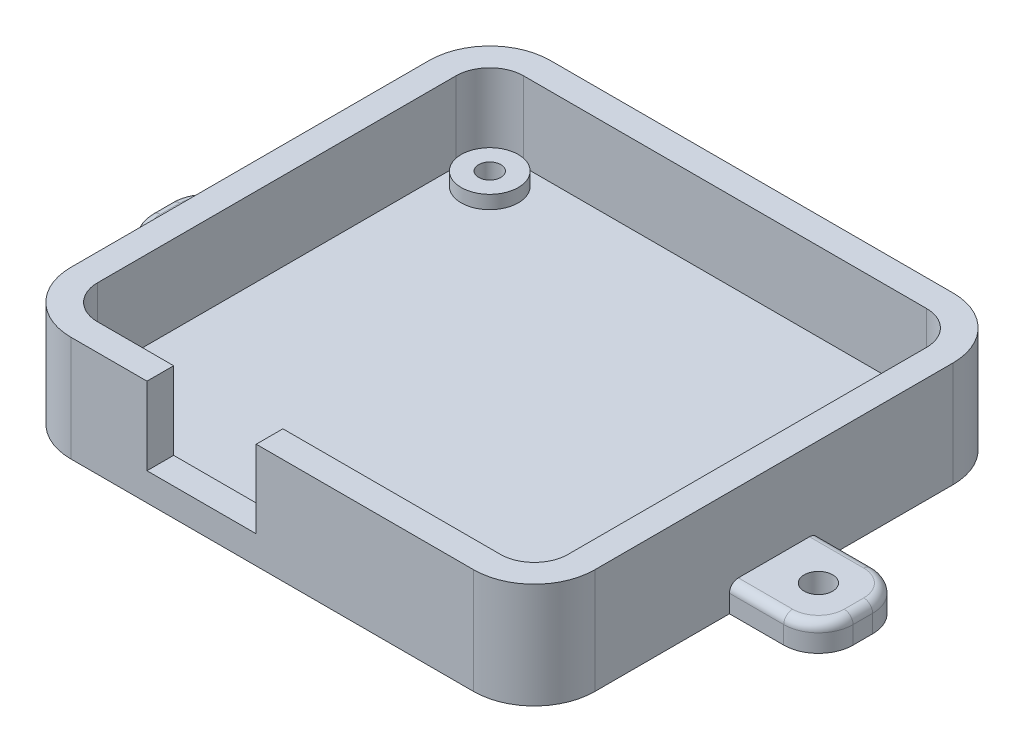
SolidWorks part; units mm, degrees
ref_plane "Front Plane" through (0, 0, 0) normal (0, 0, 1) x (1, 0, 0)
ref_plane "Top Plane" through (0, 0, 0) normal (0, 1, 0) x (1, 0, 0)
ref_plane "Right Plane" through (0, 0, 0) normal (1, 0, 0) x (0, 0, -1)
sketch "Sketch1" plane through (0, 0, 0) normal (0, 1, 0) x (1, 0, 0)
  line L0 (3.81, 3) -> (49.09, 3)
  line L1 (3.81, 0) -> (49.09, 0)
  line L2 (0, -3.81) -> (0, -44.09)
  line L3 (3.81, -47.9) -> (49.09, -47.9)
  line L4 (52.9, -3.81) -> (52.9, -44.09)
  line L5 (55.9, -3.81) -> (55.9, -44.09)
  line L6 (3.81, -50.9) -> (49.09, -50.9)
  line L7 (-3, -3.81) -> (-3, -44.09)
  arc A0 (52.9, -3.81) -> (49.09, 0) centre (49.09, -3.81) ccw
  arc A1 (0, -3.81) -> (3.81, 0) centre (3.81, -3.81) cw
  arc A2 (3.81, -47.9) -> (0, -44.09) centre (3.81, -44.09) cw
  arc A3 (52.9, -44.09) -> (49.09, -47.9) centre (49.09, -44.09) cw
  circle A4 centre (49.09, -44.09) radius 1.25
  circle A5 centre (3.81, -44.09) radius 1.25
  circle A6 centre (3.81, -3.81) radius 1.25
  circle A7 centre (49.09, -3.81) radius 1.25
  arc A8 (55.9, -3.81) -> (49.09, 3) centre (49.09, -3.81) ccw
  arc A9 (55.9, -44.09) -> (49.09, -50.9) centre (49.09, -44.09) cw
  arc A10 (3.81, -50.9) -> (-3, -44.09) centre (3.81, -44.09) cw
  arc A11 (-3, -3.81) -> (3.81, 3) centre (3.81, -3.81) cw
  circle A12 centre (3.81, -3.81) radius 3.21
  circle A13 centre (49.09, -3.81) radius 3.21
  circle A14 centre (49.09, -44.09) radius 3.21
  circle A15 centre (3.81, -44.09) radius 3.21
  point P7 (52.9, 0)
  point P10 (0, 0)
  point P15 (52.9, -47.9)
  dimension "D3" = 3.81
  dimension "D4" = 3.81
  dimension "D5" = 3.81
  dimension "D6" = 3.81
  dimension "D7" = 3
  dimension "D8" = 2.5
  dimension "D9" = 2.5
  dimension "D10" = 2.5
  dimension "D11" = 2.5
  dimension "D12" = 6.42
  dimension "D13" = 6.42
  dimension "D14" = 6.42
  dimension "D15" = 6.42
  dimension "D1" = 52.9
  dimension "D2" = 47.9
extrude "Boss-Extrude1" add sketch "Sketch1" against normal blind 3 contours L7 A10 L6 A9 L5 A8 L0 A11
extrude "Cut-Extrude1" cut sketch "Sketch1<3>" against normal up to next contours A6 | A5 | A4 | A7 region at (49.09, 0, 44.09) region at (3.81, 0, 44.09) region at (3.81, 0, 3.81) region at (49.09, 0, 3.81)
sketch "Sketch1<3>" plane through (0, 0, 0) normal (0, 1, 0) x (1, 0, 0) same geometry as "Sketch1"
extrude "Boss-Extrude2" add sketch "Sketch1<4>" along normal blind 8.86 contours A11 L7 A10 L6 A9 L5 A8 L0 L4 A3 L3 A2 L2 A1 L1 A0 region at (26.45, 0, -2.2016)
sketch "Sketch1<4>" plane through (0, 0, 0) normal (0, 1, 0) x (1, 0, 0) same geometry as "Sketch1"
extrude "Boss-Extrude3" add sketch "Sketch1<5>" along normal blind 1.5 contours A13 A7 | A14 A4 | A15 A5 | A12 A6 region at (0.6908, 0, 3.81) region at (45.9708, 0, 3.81) region at (45.9708, 0, 44.09) region at (0.6908, 0, 44.09)
sketch "Sketch1<5>" plane through (0, 0, 0) normal (0, 1, 0) x (1, 0, 0) same geometry as "Sketch1"
sketch "Sketch2" plane through (0, 0, 50.9) normal (0, 0, 1) x (1, 0, 0)
  line L0 (3.81, -3) -> (49.09, -3) construction
  line L1 (12.36, 8.865) -> (24.64, 8.865)
  line L2 (12.36, 8.865) -> (12.36, 0.135)
  line L3 (12.36, 0.135) -> (24.64, 0.135)
  line L4 (24.64, 8.865) -> (24.64, 0.135)
  line L5 (-3, -3) -> (-3, 8.86) construction
  dimension "D1" = 3.135
  dimension "D2" = 8.73
  dimension "D3" = 12.28
  dimension "D4" = 15.36
extrude "Cut-Extrude2" cut sketch "Sketch2" against normal blind 3
sketch "Sketch3" plane through (0, -3, 0) normal (0, -1, 0) x (1, 0, 0)
  line L0 (55.9, 3.81) -> (55.9, 44.09) construction
  line L1 (55.9, 18.95) -> (62, 18.95)
  line L2 (55.9, 18.95) -> (55.9, 28.95)
  line L3 (55.9, 28.95) -> (62, 28.95)
  line L4 (65.9, 22.85) -> (65.9, 25.05)
  line L5 (-3, 3.81) -> (-3, 44.09) construction
  line L6 (-3, 18.95) -> (-9.1, 18.95)
  line L7 (-3, 18.95) -> (-3, 28.95)
  line L8 (-3, 28.95) -> (-9.1, 28.95)
  line L9 (-13, 22.85) -> (-13, 25.05)
  line L10 (3.81, -3) -> (49.09, -3) construction
  circle A0 centre (60.9, 23.95) radius 1.6
  circle A1 centre (-8, 23.95) radius 1.6
  arc A2 (65.9, 22.85) -> (62, 18.95) centre (62, 22.85) cw
  arc A3 (62, 28.95) -> (65.9, 25.05) centre (62, 25.05) cw
  arc A4 (-13, 22.85) -> (-9.1, 18.95) centre (-9.1, 22.85) ccw
  arc A5 (-9.1, 28.95) -> (-13, 25.05) centre (-9.1, 25.05) ccw
  point P18 (0, 0)
  point P19 (0, 0)
  point P20 (78.1429, 16.7829)
  point P23 (65.9, 18.95)
  point P26 (65.9, 28.95)
  point P29 (-13, 18.95)
  point P32 (-13, 28.95)
  dimension "D6" = 5
  dimension "D9" = 3.9
  dimension "D10" = 3.9
  dimension "D11" = 3.9
  dimension "D12" = 3.9
  dimension "D1" = 10
  dimension "D2" = 10
  dimension "D3" = 10
  dimension "D4" = 10
  dimension "D5" = 21.95
  dimension "D7" = 5
  dimension "D8" = 5
extrude "Boss-Extrude4" add sketch "Sketch3" against normal blind 3
fillet "Fillet1" radius 1 5 edges at (58.95, 0, 18.95) (64.7577, 0, 20.0923) (65.9, 0, 23.95) (64.7577, 0, 27.8077) (58.95, 0, 28.95)
fillet "Fillet2" radius 1 5 edges at (-6.05, 0, 18.95) (-11.8577, 0, 20.0923) (-13, 0, 23.95) (-11.8577, 0, 27.8077) (-6.05, 0, 28.95)
